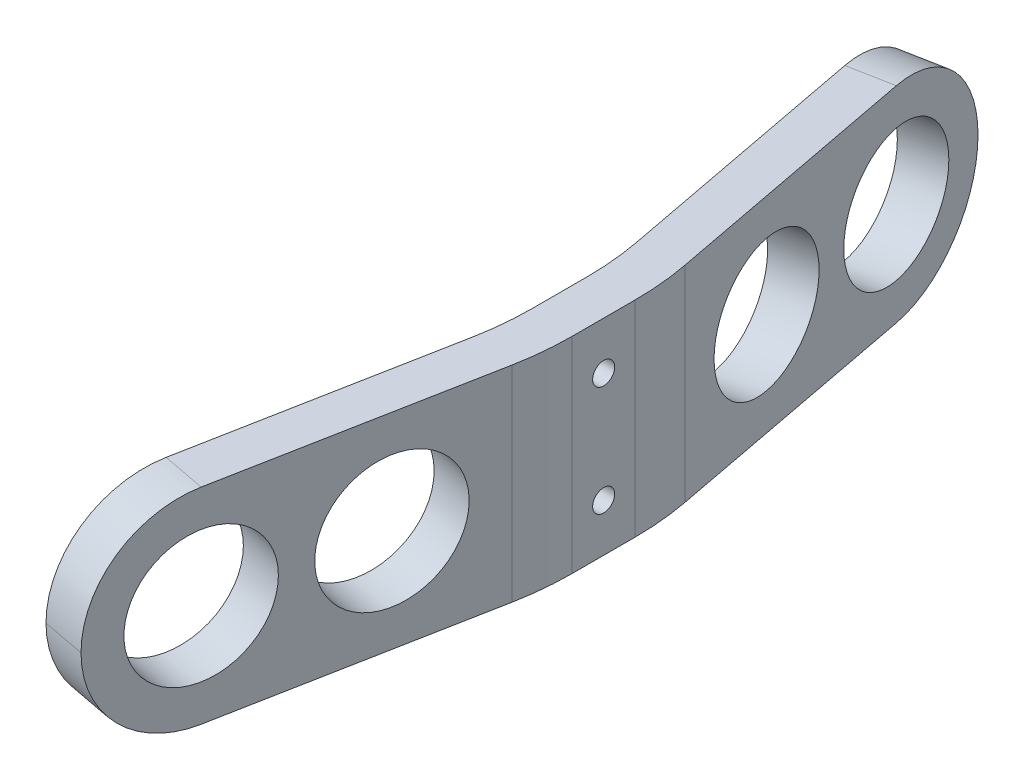
SolidWorks part; units mm, degrees
ref_plane "Front" through (0, 0, 0) normal (0, 0, 1) x (1, 0, 0)
ref_plane "Top" through (0, 0, 0) normal (0, 1, 0) x (1, 0, 0)
ref_plane "Right" through (0, 0, 0) normal (1, 0, 0) x (0, 0, -1)
sketch "Sketch1" plane through (0, 0, 0) normal (0, 1, 0) x (1, 0, 0)
  line L0 (0, -60) -> (0, 60) construction
  line L1 (0, 60) -> (10, 7.5)
  line L2 (10, 7.5) -> (10, -7.5)
  line L3 (10, -7.5) -> (0, -60)
  line L4 (0, 0) -> (10, 0) construction
  line L5 (5.894, 61.1227) -> (16, 8.0663)
  line L6 (16, 8.0663) -> (16, -8.0663)
  line L7 (16, -8.0663) -> (5.894, -61.1227)
  line L8 (0, 60) -> (5.894, 61.1227)
  line L9 (0, -60) -> (5.894, -61.1227)
  dimension "D1" = 120
  dimension "D2" = 10
  dimension "D3" = 15
  dimension "D4" = 6
extrude "Boss-Extrude1" add sketch "Sketch1" along normal blind 28
fillet "Fillet1" radius 40 4 edges at (10, 14, 7.5) (10, 14, -7.5) (16, 14, -8.0663) (16, 14, 8.0663)
sketch "Sketch2" plane through (16.9225, 0, 3.2233) normal (0.9823, 0, 0.1871) x (0.1871, 0, -0.9823)
  line L0 (-58.9403, 14) -> (-8.7057, 14) construction
  line L1 (-58.9403, 28) -> (-58.9403, 0) construction
  line L2 (-8.7057, 0) -> (-8.7057, 28) construction
  circle A0 centre (-44.9403, 14) radius 9
  circle A1 centre (-22.7057, 14) radius 9
  dimension "D1" = 18
  dimension "D2" = 18
  dimension "D3" = 14
  dimension "D4" = 14
extrude "Cut-Extrude1" cut sketch "Sketch2" against normal up to next
mirror "Mirror1" about plane through (0, 0, 0) normal (0, 0, 1) of "Cut-Extrude1"
sketch "Sketch3" plane through (16, 0, 0) normal (1, 0, 0) x (0, 0, -1)
  line L0 (0, 21.5) -> (0, 6.5) construction
  line L1 (-4.2908, 14) -> (4.2908, 14) construction
  line L2 (-4.2908, 28) -> (-4.2908, 0) construction
  line L3 (4.2908, 0) -> (4.2908, 28) construction
  circle A0 centre (0, 21.5) radius 1.5
  circle A1 centre (0, 6.5) radius 1.5
  point P11 (0, 14)
  dimension "D1" = 3
  dimension "D2" = 3
  dimension "D3" = 15
extrude "Cut-Extrude2" cut sketch "Sketch3" against normal up to next
fillet "Fillet2" radius 14 4 edges at (2.947, 0, -60.5613) (2.947, 28, -60.5613) (2.947, 0, 60.5613) (2.947, 28, 60.5613)
